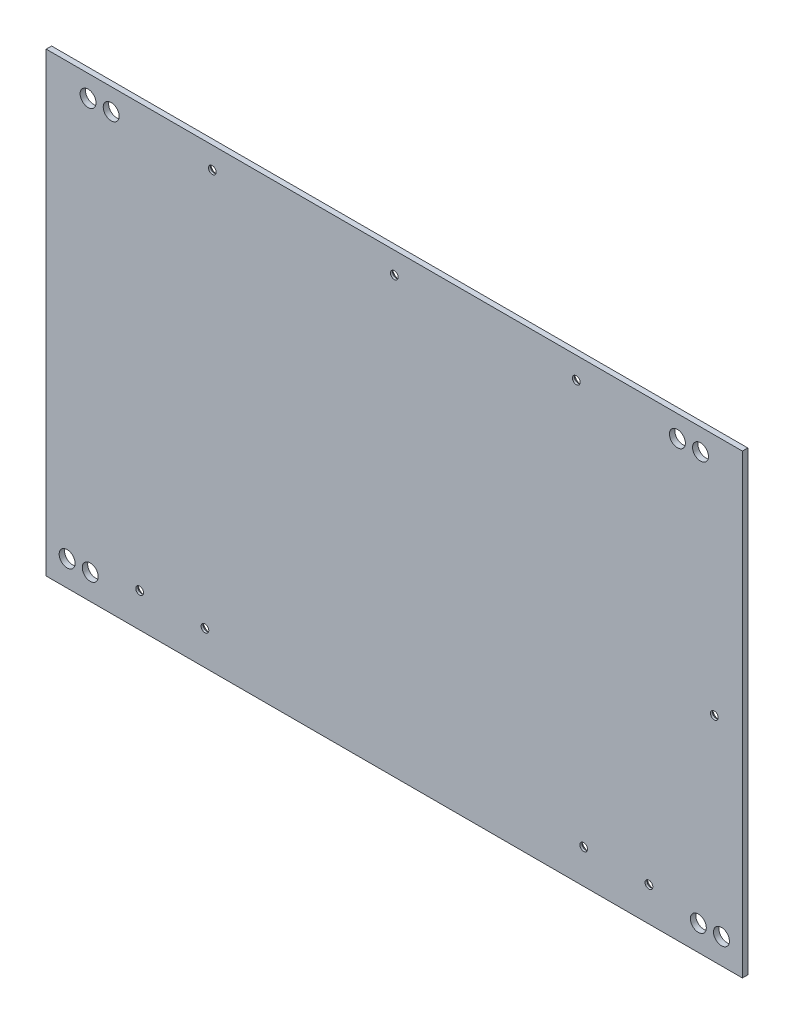
SolidWorks part; units mm, degrees
material "ABS"
ref_plane "X-Y Datum" through (0, 0, 0) normal (0, 0, 1) x (1, 0, 0)
ref_plane "X-Z Datum" through (0, 0, 0) normal (0, 1, 0) x (1, 0, 0)
ref_plane "Y-Z Datum" through (0, 0, 0) normal (1, 0, 0) x (0, 0, -1)
sketch "Sketch1" plane through (0, 0, 0) normal (0, 0, 1) x (1, 0, 0)
  line L0 (-153.025, 98.7125) -> (-153.025, -98.7125)
  line L1 (-153.025, 98.7125) -> (153.025, 98.7125)
  line L2 (-153.025, 98.7125) -> (-153.025, -98.7125)
  line L3 (-153.025, -98.7125) -> (153.025, -98.7125)
  line L4 (153.025, 98.7125) -> (153.025, -98.7125)
  line L5 (-153.025, 98.7125) -> (153.025, -98.7125) construction
  line L6 (-153.025, -98.7125) -> (153.025, 98.7125) construction
  line L7 (-153.025, -98.7125) -> (153.025, -98.7125)
  line L8 (153.025, 98.7125) -> (153.025, -98.7125)
  line L9 (-153.025, 98.7125) -> (153.025, 98.7125)
  circle A0 centre (-142.25, -87.9375) radius 10.775
  circle A1 centre (-118.25, -87.9375) radius 10.775 construction
  circle A2 centre (-130.25, -64.9375) radius 10.775
  point P0 (0, 0)
  dimension "D1" = 21.55
  dimension "D2" = 24
  dimension "D3" = 23
  dimension "D4" = 12
  dimension "D5" = 197.425
  dimension "D6" = 306.05
  dimension "D7" = 0
extrude "Boss-Extrude1" add sketch "Sketch1" along normal blind 2.3813 contours A0 L3 L4 L1 L2 A2 | A2 | A0 | A0 L2 L3 | L9 L0 L7 L8 L1 L4 L3 L2 region at (1.7287, 0.9747, 0) region at (-150.6182, -96.3057, 0) region at (-142.25, -87.9375, 0) region at (-130.25, -64.9375, 0)
sketch "Sketch9" plane through (0, 98.7125, 0) normal (0, 1, 0) x (1, 0, 0)
  line L4 (153.025, 0) -> (-153.025, 0)
  line L5 (-153.025, 0) -> (-153.025, -2.3813)
  line L6 (-153.025, -2.3813) -> (153.025, -2.3813)
  line L7 (153.025, -2.3813) -> (153.025, 0)
  line L8 (153.025, 0) -> (-153.025, 0)
  line L9 (-153.025, 0) -> (-153.025, -2.3813)
  line L10 (-153.025, -2.3813) -> (153.025, -2.3813)
  line L11 (153.025, -2.3813) -> (153.025, 0)
  dimension "D1" = 0
extrude "Boss-Extrude2" add sketch "Sketch9" along normal blind 3.175
sketch "Sketch10" plane through (0, 0, 0) normal (0, 0, -1) x (-1, 0, 0)
  circle A0 centre (-124.45, 92.3625) radius 3.5
  circle A1 centre (-134.61, 92.3625) radius 3.5
  circle A2 centre (-133.6575, -87.5375) radius 3.5
  circle A3 centre (-143.8175, -87.5375) radius 3.5
  point P0 (-143.8175, -87.5375)
  point P1 (-133.6575, -87.5375)
  point P3 (-124.45, 92.3625)
  point P5 (-134.61, 92.3625)
  point P19 (-111.94, -83.7125)
  point P20 (-83.25, -83.7125)
  point P22 (-140.6875, -4.9375)
  point P26 (-80, 92.3625)
  point P28 (80, 92.3625)
  point P30 (140.6875, 19.0625)
  point P32 (111.94, -83.7125)
  point P34 (83.25, -83.7125)
  point P36 (0.1538, -122.9407)
  point P40 (0, 92.3625)
  dimension "D1" = 7
extrude "Cut-Extrude1" cut sketch "Sketch10" against normal through all
mirror "Mirror1" about plane through (0, 0, 0) normal (1, 0, 0) of "Cut-Extrude1"
hole_wizard "CSK for M3 Flat Head Machine Screw1" positions "Sketch15" profile "Sketch12" countersink size "M3" standard "ANSI Metric" end condition through all
sketch "Sketch15" plane through (0, 0, 0) normal (0, 0, -1) x (-1, 0, 0)
  point P0 (-140.6875, -4.9375)
  point P3 (190.9076, 35.205)
  point P6 (80, 92.3625)
  point P9 (-80, 92.3625)
  point P15 (-111.94, -83.7125)
  point P18 (-83.25, -83.7125)
  point P21 (0.1538, -122.9407)
  point P24 (83.25, -83.7125)
  point P27 (111.94, -83.7125)
  point P33 (0, 92.3625)
sketch "Sketch12" plane through (140.6875, -4.9375, 0) normal (1, 0, 0) x (0, 1, 0)
  line L0 (0, 0) -> (0, 2.3812)
  line L1 (0, 2.3812) -> (1.7, 2.3812)
  line L2 (1.7, 2.3812) -> (1.7, 1.45)
  line L3 (1.7, 1.45) -> (3.15, 0)
  line L5 (3.15, 0) -> (0, 0)
  line L6 (-1.7, 1.45) -> (-3.15, 0) construction
  line L11 (0, -6.35) -> (0, 107.95) construction
  dimension "Thru Hole Dia." = 3.4
  dimension "Thru Hole Depth" = 2.3813
  dimension "Near C'Sink Dia." = 6.3
  dimension "Near C'Sink Angle" = 90
